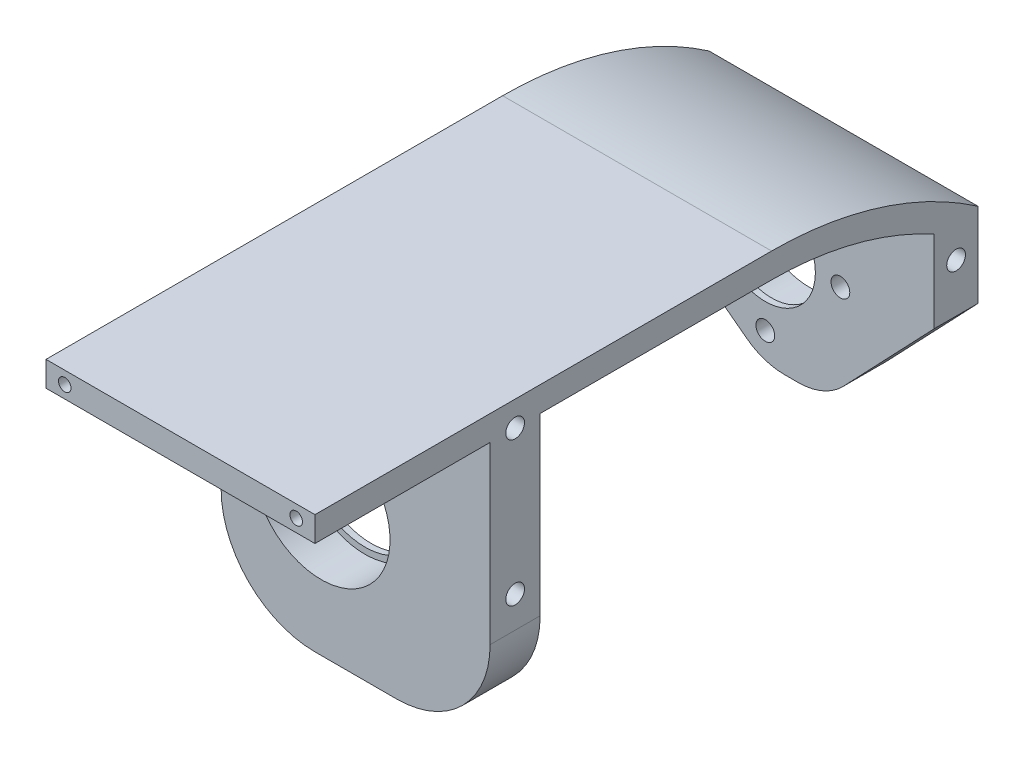
SolidWorks part; units mm, degrees
material "Polyetheretherketone (PEEK)"
ref_plane "Front Plane" through (0, 0, 0) normal (0, 0, 1) x (1, 0, 0)
ref_plane "Top Plane" through (0, 0, 0) normal (0, 1, 0) x (1, 0, 0)
ref_plane "Right Plane" through (0, 0, 0) normal (1, 0, 0) x (0, 0, -1)
sketch "Sketch3" plane through (0, 0, 0) normal (1, 0, 0) x (0, 0, -1)
  line L0 (0, 0) -> (73, 0)
  line L1 (0, 0) -> (0, -4)
  line L2 (0, -4) -> (73, -4)
  line L4 (113.6909, -22.5) -> (70.143, -22.5) construction
  line L6 (90.9961, -30.5) -> (104.9961, -30.5) construction
  line L7 (90.9961, -30.5) -> (90.9961, -14.5) construction
  line L8 (90.9961, -14.5) -> (104.9961, -14.5) construction
  line L9 (104.9961, -30.5) -> (104.9961, -14.5) construction
  line L10 (90.9961, -30.5) -> (104.9961, -14.5) construction
  line L11 (90.9961, -14.5) -> (104.9961, -30.5) construction
  line L13 (109.8205, -18.5) -> (115.4706, -18.5)
  arc A0 (73, 0) -> (115.4706, -18.5) centre (73, -58) cw
  arc A1 (73, -4) -> (104.9961, -14.5) centre (73, -58) cw
  arc A2 (104.9961, -14.5) -> (109.8205, -18.5) centre (73, -58) cw
  point P9 (97.9961, -22.5)
  dimension "D1" = 58
  dimension "D2" = 4
  dimension "D3" = 73
  dimension "D4" = 22.5
  dimension "D5" = 16
  dimension "D6" = 4
  dimension "D7" = 14
extrude "Boss-Extrude1" add sketch "Sketch3" along normal blind 43
ref_plane "Plane1" through (27.5, 0, 0) normal (1, 0, 0) x (0, 0, -1)
sketch "Sketch4" plane through (43, 0, 0) normal (1, 0, 0) x (0, 0, -1)
  line L0 (28, -4) -> (28, -14.5)
  line L1 (0, -4) -> (73, -4) construction
  line L2 (114.75, -23.7518) -> (114.75, -33.7153) construction
  line L3 (0, 0) -> (0, -4) construction
  line L4 (28, -4) -> (36, -4)
  line L5 (36, -4) -> (36, -15.5)
  line L6 (36, -15.5) -> (35, -15.5) construction
  line L7 (35, -15.5) -> (35, -14.5) construction
  line L8 (35, -14.5) -> (28, -14.5) construction
  line L9 (35, -15.5) -> (35, -25.5) construction
  line L10 (35, -25.5) -> (17.1507, -25.5) construction
  line L11 (28, -14.5) -> (28, -36.5)
  line L12 (36, -15.5) -> (36, -35.5)
  line L13 (28, -47) -> (36, -47)
  line L14 (28, -47) -> (28, -36.5)
  line L15 (36, -47) -> (36, -35.5)
  line L16 (73, 0) -> (0, 0) construction
  arc A0 (109.8205, -18.5) -> (73, -4) centre (73, -58) ccw construction
  point P22 (28, -25.5)
  point P23 (36, -25.5)
  dimension "D1" = 28
  dimension "D2" = 114.75
  dimension "D3" = 25.5
  dimension "D4" = 8
  dimension "D5" = 7
  dimension "D6" = 11.5
  dimension "D7" = 11
extrude "Boss-Extrude3" add sketch "Sketch4" against normal up to surface (43 mm away) contours L11 L14 L13 L15 L12 L5 L4 L0 up to face at (0, -6.1802, -62.4324)
sketch "Sketch5" plane through (0, 0, -28) normal (0, 0, 1) x (1, 0, 0)
  line L0 (43, -25.5) -> (27, -25.5) construction
  line L1 (43, -47) -> (43, -4) construction
  line L2 (0, -47) -> (0, -4) construction
  circle A0 centre (27, -25.5) radius 11
  dimension "D2" = 22
  dimension "D1" = 27
  dimension "D3" = 21.5
extrude "Cut-Extrude1" cut sketch "Sketch5" against normal blind 7
sketch "Sketch6" plane through (0, 0, -35) normal (0, 0, 1) x (1, 0, 0)
  circle A0 centre (27, -25.5) radius 10
  dimension "D1" = 20
extrude "Cut-Extrude2" cut sketch "Sketch6" against normal blind 7
sketch "Sketch7" plane through (43, 0, 0) normal (1, 0, 0) x (0, 0, -1)
  line L0 (36, -4) -> (99, -4) construction
  line L1 (99, -4) -> (99, -10.6714) construction
  line L2 (67.5, -4) -> (67.5, -25.5) construction
  line L3 (67.5, -25.5) -> (116.1248, -25.5) construction
  line L4 (99, -10.6714) -> (99, -16) construction
  line L5 (99, -16) -> (105, -16) construction
  line L6 (105, -16) -> (105, -17.5) construction
  line L7 (105, -17.5) -> (106, -17.5) construction
  line L8 (106, -17.5) -> (106, -15.2566) construction
  line L9 (99, -10.6714) -> (99, -47)
  line L10 (99, -47) -> (106, -47)
  line L11 (106, -47) -> (106, -15.2566)
  arc A0 (109.8205, -18.5) -> (73, -4) centre (73, -58) ccw construction
  arc A2 (106, -15.2566) -> (99, -10.6714) centre (73, -58) ccw
  dimension "D1" = 63
  dimension "D2" = 21.5
  dimension "D3" = 9.5
  dimension "D4" = 8
  dimension "D5" = 6
  dimension "D6" = 1
  dimension "D7" = 43
extrude "Boss-Extrude4" add sketch "Sketch7" against normal up to surface (43 mm away) contours L11 A2 L9 L10 up to face at (0, -13.9081, -50.2594)
sketch "Sketch8" plane through (0, 0, -106) normal (0, 0, 1) x (1, 0, 0)
  circle A0 centre (27, -25.5) radius 9.5
  dimension "D1" = 19
extrude "Cut-Extrude3" cut sketch "Sketch8" along normal blind 6
sketch "Sketch9" plane through (0, 0, -100) normal (0, 0, -1) x (-1, 0, 0)
  circle A0 centre (-27, -25.5) radius 8
  dimension "D1" = 16
extrude "Cut-Extrude4" cut sketch "Sketch9" against normal blind 1
sketch "Sketch10" plane through (0, 0, -106) normal (0, 0, -1) x (-1, 0, 0)
  line L0 (0, -23.7577) -> (-17.4711, -42.0819)
  line L1 (0, -47) -> (0, -15.2566) construction
  line L2 (-17.4711, -42.0819) -> (-27.3185, -42.0819)
  line L3 (-27.3185, -42.0819) -> (-43, -30.2284)
  line L4 (-43, -47) -> (-43, -15.2566) construction
  line L5 (-43, -30.2284) -> (-43, -47)
  line L6 (-43, -47) -> (0, -47)
  line L7 (0, -47) -> (0, -23.7577)
extrude "Cut-Extrude5" cut sketch "Sketch10" against normal up to surface (7 mm away) up to face at (19, -25.5, -99)
sketch "Sketch11" plane through (43, 0, 0) normal (1, 0, 0) x (0, 0, -1)
  line L0 (106, -15.2566) -> (106, -10.303)
  line L1 (109.8205, -18.5) -> (115.4706, -18.5) construction
  line L2 (109.8205, -18.5) -> (115.4706, -18.5)
  arc A0 (115.4706, -18.5) -> (73, 0) centre (73, -58) ccw construction
  arc A1 (109.8205, -18.5) -> (106, -15.2566) centre (73, -58) ccw construction
  arc A2 (109.8205, -18.5) -> (106, -15.2566) centre (73, -58) ccw
  arc A3 (115.4706, -18.5) -> (106, -10.303) centre (73, -58) ccw
extrude "Cut-Extrude6" cut sketch "Sketch11" against normal through all
fillet "Fillet2" radius 10 2 edges at (17.4711, -42.0819, -102.5) (27.3185, -42.0819, -102.5)
sketch "Sketch12" plane through (0, 0, -99) normal (0, 0, 1) x (1, 0, 0)
  line L0 (27, -25.5) -> (27, -13.5) construction
  circle A0 centre (27, -13.5) radius 1.5
  circle A1 centre (39, -25.5) radius 1.5
  circle A2 centre (27, -37.5) radius 1.5
  circle A3 centre (15, -25.5) radius 1.5
  point P12 (27, -25.5)
  dimension "D1" = 3
  dimension "D3" = 12
  dimension "D4" = 12
  dimension "D5" = 12
  dimension "D2" = 4
extrude "Cut-Extrude7" cut sketch "Sketch12" against normal through all
sketch "Sketch13" [suppressed] plane through (0, 0, -28) normal (0, 0, 1) x (1, 0, 0)
  line L0 (23, 0) -> (23, -29) construction
  line L1 (37, 0) -> (0, 0) construction
  line L3 (0, -47) -> (0, -4) construction
  circle A0 centre (23, -29) radius 11
  dimension "D2" = 22
  dimension "D1" = 29
  dimension "D3" = 23
extrude "Cut-Extrude8" [suppressed] cut sketch "Sketch13" against normal blind 7 contours A0
sketch "Sketch14" [suppressed] plane through (0, 0, -35) normal (0, 0, 1) x (1, 0, 0)
  circle A0 centre (23, -29) radius 10
  dimension "D1" = 20
extrude "Cut-Extrude9" [suppressed] cut sketch "Sketch14" against normal blind 7
sketch "Sketch15" [suppressed] plane through (0, 0, 0) normal (-1, 0, 0) x (0, 0, 1)
  line L0 (-97, -8.2506) -> (-97, -47)
  line L1 (-97, -47) -> (-104, -47)
  line L2 (-104, -47) -> (-104, -11.8264)
  line L3 (-36, -4) -> (-36, -47) construction
  line L4 (-28, -47) -> (-36, -47) construction
  arc A0 (-76, -4) -> (-112.8205, -18.5) centre (-76, -58) ccw construction
  arc A1 (-97, -8.2506) -> (-104, -11.8264) centre (-76, -58) ccw
  dimension "D1" = 61
  dimension "D2" = 7
extrude "Boss-Extrude5" [suppressed] add sketch "Sketch15" against normal up to surface (37 mm away) up to face at (43, -15.6062, -57.1006)
sketch "Sketch16" [suppressed] plane through (0, 0, -97) normal (0, 0, 1) x (1, 0, 0)
  circle A0 centre (23, -29) radius 8
  dimension "D1" = 16
extrude "Cut-Extrude10" [suppressed] cut sketch "Sketch16" against normal blind 1
sketch "Sketch17" [suppressed] plane through (0, 0, -98) normal (0, 0, 1) x (1, 0, 0)
  circle A0 centre (23, -29) radius 9.5
  dimension "D1" = 19
extrude "Cut-Extrude11" [suppressed] cut sketch "Sketch17" against normal through all
sketch "Sketch18" [suppressed] plane through (37, 0, 0) normal (1, 0, 0) x (0, 0, -1)
  line L0 (104, -11.8264) -> (104, -7.2063)
  line L1 (112.8205, -18.5) -> (118.4706, -18.5) construction
  line L2 (112.8205, -18.5) -> (118.4706, -18.5)
  arc A0 (118.4706, -18.5) -> (76, 0) centre (76, -58) ccw construction
  arc A1 (112.8205, -18.5) -> (104, -11.8264) centre (76, -58) ccw construction
  arc A2 (118.4706, -18.5) -> (104, -7.2063) centre (76, -58) ccw
  arc A3 (112.8205, -18.5) -> (104, -11.8264) centre (76, -58) ccw
extrude "Cut-Extrude12" [suppressed] cut sketch "Sketch18" against normal through all
sketch "Sketch19" [suppressed] plane through (0, 0, -104) normal (0, 0, -1) x (-1, 0, 0)
  line L0 (-23, -29) -> (-23, -17) construction
  circle A0 centre (-23, -17) radius 1.5
  circle A1 centre (-11, -29) radius 1.5
  circle A2 centre (-23, -41) radius 1.5
  circle A3 centre (-35, -29) radius 1.5
  point P12 (-23, -29)
  dimension "D1" = 3
  dimension "D2" = 12
  dimension "D4" = 12
  dimension "D5" = 12
  dimension "D3" = 4
extrude "Cut-Extrude13" [suppressed] cut sketch "Sketch19" against normal up to surface (7 mm away)
fillet "Fillet3" [suppressed] radius 10
fillet "Fillet4" [suppressed] radius 10
fillet "Fillet5" radius 15 2 edges at (0, -47, -32) (43, -47, -32)
sketch "Sketch20" plane through (0, 0, 0) normal (-1, 0, 0) x (0, 0, 1)
  line L0 (-28, -4) -> (-36, -4) construction
  line L1 (-99, -10.6714) -> (-106, -10.6714) construction
  line L2 (-106, -23.7577) -> (-106, -10.303) construction
  line L3 (-102.5, -10.6714) -> (-102.5, -16) construction
  line L4 (-73, 0) -> (0, 0) construction
  line L5 (-32, -4) -> (-32, 0) construction
  line L6 (-32, -32) -> (-32, -27) construction
  line L7 (-36, -32) -> (-28, -32) construction
  line L8 (0, 0) -> (0, -4) construction
  circle A0 centre (-32, -4) radius 1.5
  circle A1 centre (-102.5, -16) radius 1.5
  circle A2 centre (-32, -27) radius 1.5
  dimension "D1" = 3
  dimension "D2" = 3
  dimension "D5" = 3
  dimension "D3" = 16
  dimension "D4" = 5
  dimension "D6" = 23
  dimension "D7" = 32
  dimension "D8" = 102.5
extrude "Cut-Extrude14" cut sketch "Sketch20" against normal blind 6
sketch "Sketch21" plane through (0, 0, 0) normal (0, 0, 1) x (1, 0, 0)
  line L0 (0, 0) -> (0, -4) construction
  line L1 (0, -2) -> (3, -2) construction
  line L2 (43, -2) -> (40, -2) construction
  line L3 (43, 0) -> (43, -4) construction
  circle A0 centre (3, -2) radius 1
  circle A1 centre (40, -2) radius 1
  dimension "D2" = 2
  dimension "D4" = 2
  dimension "D1" = 3
  dimension "D3" = 3
  dimension "D5" = 37
extrude "Cut-Extrude15" cut sketch "Sketch21" against normal blind 6 contours A0 | A1
sketch "Sketch22" [suppressed] plane through (0, 0, 0) normal (-1, 0, 0) x (0, 0, 1)
  line L0 (-97, -8.2506) -> (-104, -8.2506) construction
  line L1 (-104, -7.2063) -> (-104, -37) construction
  line L2 (-36, -4) -> (-28, -4) construction
  line L3 (-76, 0) -> (0, 0) construction
  circle A0 centre (-100.5, -16) radius 1.5
  circle A1 centre (-32, -4) radius 1.5
  circle A2 centre (-32, -27) radius 1.5
  point P7 (-100.5, -8.2506)
  dimension "D2" = 3
  dimension "D3" = 3
  dimension "D5" = 3
  dimension "D1" = 16
  dimension "D4" = 23
extrude "Cut-Extrude16" [suppressed] cut sketch "Sketch22" against normal blind 6
mirror "Mirror1" about plane through (43, -58, -73) normal (-1, 0, 0) of bodies 121
delete or keep bodies "Body-Delete/Keep 1" type delete bodies bodies 121
mirror "Mirror2" [suppressed] of bodies 122
delete or keep bodies "Body-Delete/Keep 2" [suppressed] type delete bodies bodies 122
equation "\"mini-flipper-shaft-diameter\"= 26mm"
equation "\"mini-shaft-ring-groove-diam\"= 7.8mm"
equation "\"mini-shaft-ring-groove-width\"= 1mm"
equation "\"dtCoverPlate-DistFrom-GearCent\"= 73mm"
equation "\"wormGearShaft-L\"= \"dtCoverPlate-DistFrom-GearCent\" - 27.75 + 3.75"
equation "\"wormGearShaft-Dsmall\"= 6mm"
equation "\"wormGearShaft-Dworm\"= 12mm"
equation "\"wormL-D\" = 12mm"
equation "\"wormR-D\" = 15mm"
equation "\"wormGearL-D\" = 46mm"
equation "\"wormGearR-D\" = 50mm"
equation "\"D1@Sketch13\"=58-(\"wormGearL-D\"/2+\"wormL-D\"/2)"
